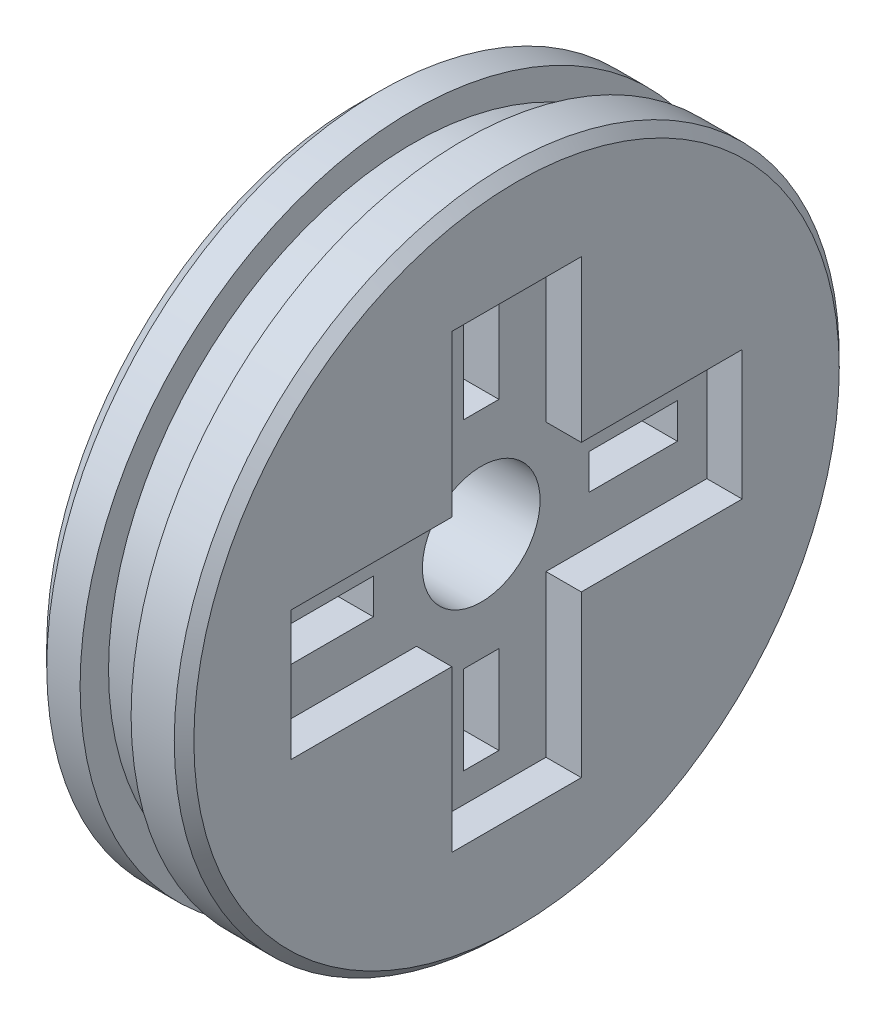
SolidWorks part; units mm, degrees
ref_plane "Front Plane" through (0, 0, 0) normal (0, 0, 1) x (1, 0, 0)
ref_plane "Top Plane" through (0, 0, 0) normal (0, 1, 0) x (1, 0, 0)
ref_plane "Right Plane" through (0, 0, 0) normal (1, 0, 0) x (0, 0, -1)
ref_plane "Plane1" through (0, 0, 66) normal (0, 0, 1) x (1, 0, 0)
sketch "Sketch1" plane through (0, 0, 66) normal (0, 0, 1) x (1, 0, 0)
  line L0 (-90.2, -65) -> (-72.2, -65) construction
  line L1 (-77.2, -65) -> (-85.2, -65)
  line L2 (-85.2, -65) -> (-85.2, -49.05)
  line L3 (-85.2, -49.05) -> (-84.2, -48.05)
  line L4 (-84.2, -48.05) -> (-77.7, -48.05)
  line L5 (-77.7, -48.05) -> (-77.2, -48.55)
  line L6 (-77.2, -48.55) -> (-77.2, -65)
revolve "Revolve1" add sketch "Sketch1" angle 360 about L0
sketch "Sketch2" plane through (0, 0, 66) normal (0, 0, 1) x (1, 0, 0)
  line L0 (-87.5, -65) -> (-74.9, -65) construction
  line L1 (-79.9, -49.5) -> (-82.5, -49.5)
  line L2 (-82.5, -49.5) -> (-82.5, -47.05)
  line L3 (-82.5, -47.05) -> (-79.9, -47.05)
  line L4 (-79.9, -47.05) -> (-79.9, -49.5)
revolve "Revolve2" add sketch "Sketch2" angle 360 about L0
combine bodies "Combine1" operation type subtract main body 101 bodies to subtract 102
sketch "Sketch3" plane through (0, 0, 0) normal (0, 0, 1) x (1, 0, 0)
  line L1 (-79, -76.5) -> (-76.7, -76.5)
  line L2 (-79, -76.5) -> (-79, -53.5)
  line L3 (-79, -53.5) -> (-76.7, -53.5)
  line L4 (-76.7, -76.5) -> (-76.7, -53.5)
extrude "Boss-Extrude1" add sketch "Sketch3" along normal blind 6.6 from offset 62.7 separate body
combine bodies "Combine2" operation type subtract main body 103 bodies to subtract 104
sketch "Sketch4" plane through (0, 0, 0) normal (0, 0, 1) x (1, 0, 0)
  line L1 (-79, -68.3) -> (-76.7, -68.3)
  line L2 (-79, -68.3) -> (-79, -61.7)
  line L3 (-79, -61.7) -> (-76.7, -61.7)
  line L4 (-76.7, -68.3) -> (-76.7, -61.7)
extrude "Boss-Extrude2" add sketch "Sketch4" along normal blind 23 from offset 54.5 separate body
combine bodies "Combine3" operation type subtract main body 105 bodies to subtract 106
sketch "Sketch5" plane through (0, 0, 0) normal (1, 0, 0) x (0, 0, -1)
  circle A0 centre (-66, -65) radius 4.6
extrude "Boss-Extrude3" add sketch "Sketch5" along normal blind 2.3 from offset 79 separate body offset against normal yes
combine bodies "Combine4" operation type subtract main body 107 bodies to subtract 108
sketch "Sketch6" plane through (0, 0, 0) normal (1, 0, 0) x (0, 0, -1)
  circle A0 centre (-66, -65) radius 7.1
extrude "Boss-Extrude4" add sketch "Sketch6" along normal blind 1.7 from offset 85.7 separate body offset against normal yes
combine bodies "Combine5" operation type subtract main body 109 bodies to subtract 110
sketch "Sketch7" plane through (0, 0, 0) normal (1, 0, 0) x (0, 0, -1)
  circle A0 centre (-66, -65) radius 3
extrude "Boss-Extrude5" add sketch "Sketch7" along normal blind 5.2 from offset 84.1 separate body offset against normal yes
combine bodies "Combine6" operation type subtract main body 111 bodies to subtract 112
sketch "Sketch8" plane through (0, 0, 0) normal (0, 0, 1) x (1, 0, 0)
  line L1 (-83, -59.5) -> (-78.9, -59.5)
  line L2 (-83, -59.5) -> (-83, -57.4)
  line L3 (-83, -57.4) -> (-78.9, -57.4)
  line L4 (-78.9, -59.5) -> (-78.9, -57.4)
extrude "Boss-Extrude6" add sketch "Sketch8" along normal blind 1.8 from offset 65.1 separate body
combine bodies "Combine7" operation type subtract main body 113 bodies to subtract 114
sketch "Sketch9" plane through (0, 0, 0) normal (0, 0, 1) x (1, 0, 0)
  line L1 (-83, -65.9) -> (-78.9, -65.9)
  line L2 (-83, -65.9) -> (-83, -64.1)
  line L3 (-83, -64.1) -> (-78.9, -64.1)
  line L4 (-78.9, -65.9) -> (-78.9, -64.1)
extrude "Boss-Extrude7" add sketch "Sketch9" along normal blind 2.1 from offset 71.5 separate body
combine bodies "Combine8" operation type subtract main body 115 bodies to subtract 116
sketch "Sketch10" plane through (0, 0, 0) normal (0, 0, 1) x (1, 0, 0)
  line L1 (-83, -72.6) -> (-78.9, -72.6)
  line L2 (-83, -72.6) -> (-83, -70.5)
  line L3 (-83, -70.5) -> (-78.9, -70.5)
  line L4 (-78.9, -72.6) -> (-78.9, -70.5)
extrude "Boss-Extrude8" add sketch "Sketch10" along normal blind 1.8 from offset 65.1 separate body
combine bodies "Combine9" operation type subtract main body 117 bodies to subtract 118
sketch "Sketch11" plane through (0, 0, 0) normal (0, 0, 1) x (1, 0, 0)
  line L1 (-83, -65.9) -> (-78.9, -65.9)
  line L2 (-83, -65.9) -> (-83, -64.1)
  line L3 (-83, -64.1) -> (-78.9, -64.1)
  line L4 (-78.9, -65.9) -> (-78.9, -64.1)
extrude "Boss-Extrude9" add sketch "Sketch11" along normal blind 2.1 from offset 58.4 separate body
combine bodies "Combine10" operation type subtract main body 119 bodies to subtract 120
sketch "Sketch12" plane through (0, 0, 0) normal (0, 0, 1) x (1, 0, 0)
  line L1 (-84.2, -57.4) -> (-78.9, -57.4)
  line L2 (-84.2, -57.4) -> (-84.2, -55)
  line L3 (-84.2, -55) -> (-78.9, -55)
  line L4 (-78.9, -57.4) -> (-78.9, -55)
extrude "Boss-Extrude10" add sketch "Sketch12" along normal blind 1.8 from offset 65.1 separate body
combine bodies "Combine11" operation type subtract main body 121 bodies to subtract 122
sketch "Sketch13" plane through (0, 0, 0) normal (0, 0, 1) x (1, 0, 0)
  line L1 (-84.2, -65.9) -> (-78.9, -65.9)
  line L2 (-84.2, -65.9) -> (-84.2, -64.1)
  line L3 (-84.2, -64.1) -> (-78.9, -64.1)
  line L4 (-78.9, -65.9) -> (-78.9, -64.1)
extrude "Boss-Extrude11" add sketch "Sketch13" along normal blind 2.4 from offset 73.6 separate body
combine bodies "Combine12" operation type subtract main body 123 bodies to subtract 124
sketch "Sketch14" plane through (0, 0, 0) normal (0, 0, 1) x (1, 0, 0)
  line L1 (-84.2, -75) -> (-78.9, -75)
  line L2 (-84.2, -75) -> (-84.2, -72.6)
  line L3 (-84.2, -72.6) -> (-78.9, -72.6)
  line L4 (-78.9, -75) -> (-78.9, -72.6)
extrude "Boss-Extrude12" add sketch "Sketch14" along normal blind 1.8 from offset 65.1 separate body
combine bodies "Combine13" operation type subtract main body 125 bodies to subtract 126
sketch "Sketch15" plane through (0, 0, 0) normal (0, 0, 1) x (1, 0, 0)
  line L1 (-84.2, -65.9) -> (-78.9, -65.9)
  line L2 (-84.2, -65.9) -> (-84.2, -64.1)
  line L3 (-84.2, -64.1) -> (-78.9, -64.1)
  line L4 (-78.9, -65.9) -> (-78.9, -64.1)
extrude "Boss-Extrude13" add sketch "Sketch15" along normal blind 2.4 from offset 56 separate body
combine bodies "Combine14" operation type subtract main body 127 bodies to subtract 128
